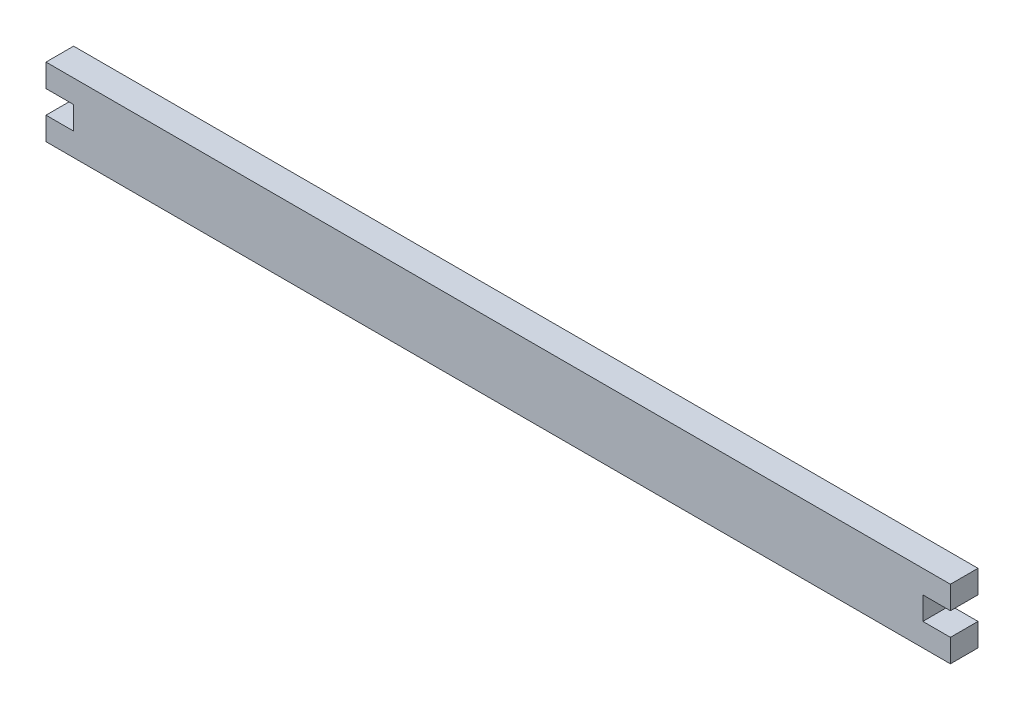
SolidWorks part; units mm, degrees
material "Teak"
ref_plane "Front Plane" through (0, 0, 0) normal (0, 0, 1) x (1, 0, 0)
ref_plane "Top Plane" through (0, 0, 0) normal (0, 1, 0) x (1, 0, 0)
ref_plane "Right Plane" through (0, 0, 0) normal (1, 0, 0) x (0, 0, -1)
sketch "Sketch1" plane through (0, 0, 0) normal (0, 0, 1) x (1, 0, 0)
  line L1 (-295, 22.5) -> (295, 22.5)
  line L2 (-295, 22.5) -> (-295, -22.5)
  line L3 (-295, -22.5) -> (295, -22.5)
  line L4 (295, 22.5) -> (295, -22.5)
  line L5 (-295, 22.5) -> (295, -22.5) construction
  line L6 (-295, -22.5) -> (295, 22.5) construction
  point P0 (0, 0)
  dimension "D1" = 590
  dimension "D2" = 45
extrude "Основа" add sketch "Sketch1" along normal blind 18
sketch "Sketch2" plane through (0, 0, 18) normal (0, 0, 1) x (1, 0, 0)
  line L0 (-295, -7.5) -> (-277, -7.5)
  line L1 (-295, 22.5) -> (-295, -22.5) construction
  line L2 (-277, -7.5) -> (-277, 7.5)
  line L3 (-277, 7.5) -> (-295, 7.5)
  line L4 (-295, 7.5) -> (-295, -7.5)
  line L5 (0, 22.5) -> (0, -22.5) construction
  line L6 (295, 22.5) -> (-295, 22.5) construction
  line L7 (-295, -22.5) -> (295, -22.5) construction
  point P13 (-295, 0)
  point P14 (-295, 0)
  dimension "D1" = 18
  dimension "D2" = 15
extrude "Шип" cut sketch "Sketch2" against normal up to next
sketch "Sketch3" plane through (0, 0, 18) normal (0, 0, 1) x (1, 0, 0)
  line L0 (-277, 7.5) -> (-295, 7.5) construction
  line L1 (-295, 22.5) -> (-295, 7.5) construction
  line L2 (-295, -7.5) -> (-295, -22.5) construction
  circle A0 centre (-286, 15) radius 1.75
  circle A1 centre (-286, -15) radius 1.75
  point P7 (-286, 7.5)
  point P12 (-295, 15)
  point P16 (-295, -15)
  dimension "D1" = 3.5
extrude "Крепежные" [suppressed] cut sketch "Sketch3" against normal up to next
mirror "Mirror1" about plane through (0, 0, 0) normal (1, 0, 0) of "Крепежные", "Шип"
